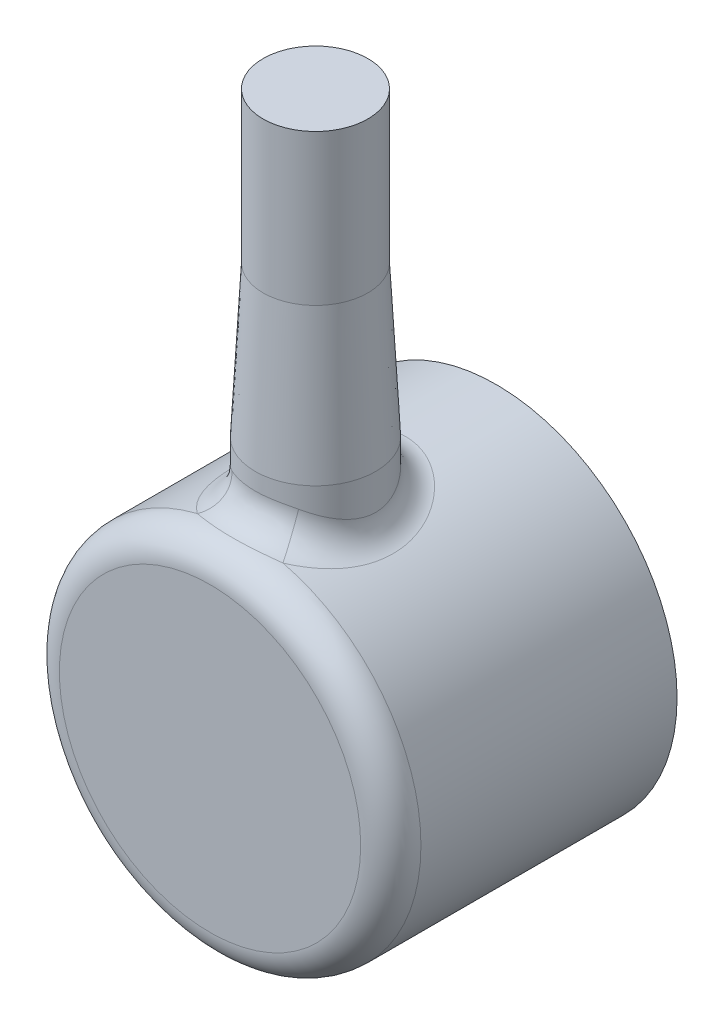
SolidWorks part; units mm, degrees
ref_plane "Plan de face" through (0, 0, 0) normal (0, 0, 1) x (1, 0, 0)
ref_plane "Plan de dessus" through (0, 0, 0) normal (0, 1, 0) x (1, 0, 0)
ref_plane "Plan de droite" through (0, 0, 0) normal (1, 0, 0) x (0, 0, -1)
sketch "Esquisse1" plane through (0, 0, 0) normal (0, 0, 1) x (1, 0, 0)
  circle A0 centre (0, 0) radius 12
  dimension "D1" = 24
extrude "Boss.-Extru.1" add sketch "Esquisse1" along normal blind 19
fillet "Congé1" radius 2 1 edges at (12, 0, 19)
sketch "Esquisse2" plane through (0, 0, 0) normal (0, 0, -1) x (-1, 0, 0)
  circle A0 centre (0, 0) radius 9.5
  dimension "D1" = 19
extrude "Enlèv. mat.-Extru.1" cut sketch "Esquisse2" against normal blind 1
sketch "Esquisse3" plane through (0, 0, 1) normal (0, 0, -1) x (-1, 0, 0)
  line L0 (0, 0) -> (0, 7.9161) construction
  line L1 (2, 0) -> (-2, 0) construction
  line L2 (2, 2.5) -> (-2, 2.5) construction
  line L3 (2, 1.5) -> (2, -1.5)
  line L4 (2, -2.5) -> (-2, -2.5) construction
  line L5 (-2, 1.5) -> (-2, -1.5)
  line L6 (0, 2.5) -> (0, -2.5) construction
  arc A0 (2, 1.5) -> (-2, 1.5) centre (0, 0) ccw
  arc A1 (-2, -1.5) -> (2, -1.5) centre (0, 0) ccw
  dimension "D1" = 5
  dimension "D2" = 5
  dimension "D3" = 4
  dimension "D4" = 3
  dimension "D5" = 3
extrude "Boss.-Extru.2" add sketch "Esquisse3" along normal blind 4
sketch "Esquisse4" plane through (0, 0, -3) normal (0, 0, -1) x (-1, 0, 0)
  circle A0 centre (0, 0) radius 1
  dimension "D1" = 2
extrude "Enlèv. mat.-Extru.2" cut sketch "Esquisse4" against normal blind 4
sketch "Esquisse5" plane through (0, 0, 1) normal (0, 0, -1) x (-1, 0, 0)
  line L0 (0, 0) -> (0, 21.4576) construction
  circle A0 centre (0, 7) radius 1
  circle A1 centre (0, -7) radius 1
  point P10 (0, 0)
  dimension "D1" = 2
  dimension "D2" = 7
  dimension "D3" = 2
extrude "Enlèv. mat.-Extru.3" cut sketch "Esquisse5" against normal blind 4
sketch "Esquisse6" plane through (0, 0, 0) normal (0, 1, 0) x (1, 0, 0)
  line L0 (0, 0) -> (0, -24.459) construction
  line L1 (12, 0) -> (-12, 0) construction
  circle A0 centre (0, -12) radius 4
  dimension "D1" = 8
  dimension "D2" = 12
extrude "Boss.-Extru.3" add sketch "Esquisse6" along normal blind 15
fillet "Congé2" radius 2 1 edges at (0.6797, 11.9807, 15.9418)
sketch "Esquisse8" plane through (0, 15, 0) normal (0, 1, 0) x (1, 0, 0)
  circle A1 centre (0, -12) radius 4
  circle A2 centre (0, -12) radius 4
  dimension "D1" = 0
extrude "Boss.-Extru.4" add sketch "Esquisse8" along normal blind 10 draft 3
sketch "Esquisse9" plane through (0, 25, 0) normal (0, 1, 0) x (1, 0, 0)
  circle A1 centre (0, -12) radius 3.4759
  circle A2 centre (0, -12) radius 3.4759
  dimension "D1" = 0
extrude "Boss.-Extru.5" add sketch "Esquisse9" along normal blind 10
